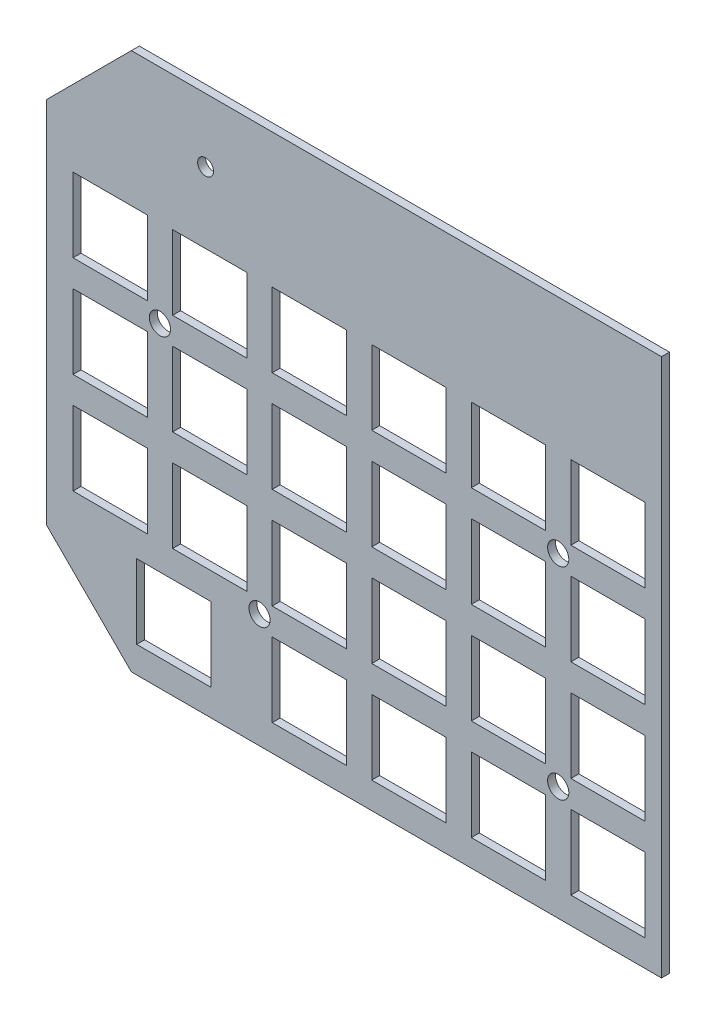
SolidWorks part; units mm, degrees
ref_plane "Plan de face" through (0, 0, 0) normal (0, 0, 1) x (1, 0, 0)
ref_plane "Plan de dessus" through (0, 0, 0) normal (0, 1, 0) x (1, 0, 0)
ref_plane "Plan de droite" through (0, 0, 0) normal (1, 0, 0) x (0, 0, -1)
sketch "Esquisse1" plane through (0, 0, 0) normal (0, 0, 1) x (1, 0, 0)
  line L0 (0, -85) -> (16, -101)
  line L4 (116, 0.5) -> (116, -101)
  line L5 (16, 0.5) -> (0, -15.5)
  line L7 (116, 0.5) -> (16, 0.5)
  line L8 (0, -15.5) -> (0, -85)
  line L9 (16, -101) -> (116, -101)
  dimension "D1" = 101.5
  dimension "D2" = 116
  dimension "D3" = 16
  dimension "D4" = 16
  dimension "D5" = 16
  dimension "D6" = 16
extrude "Boss.-Extru.1" add sketch "Esquisse1" along normal blind 1.5
sketch "Esquisse2" plane through (0, 0, 1.5) normal (0, 0, 1) x (1, 0, 0)
  line L0 (0, -15.5) -> (0, -85) construction
  line L1 (5, -24.85) -> (19, -24.85)
  line L2 (5, -24.85) -> (5, -38.85)
  line L3 (5, -38.85) -> (19, -38.85)
  line L4 (19, -24.85) -> (19, -38.85)
  line L5 (12, -38.85) -> (12, -24.85) construction
  line L6 (5, -31.85) -> (19, -31.85) construction
  line L7 (116, 0.5) -> (16, 0.5) construction
  line L12 (23.7813, -24.85) -> (23.7813, -38.85)
  line L13 (23.7813, -24.85) -> (37.7813, -24.85)
  line L14 (37.7813, -24.85) -> (37.7813, -38.85)
  line L15 (23.7813, -38.85) -> (37.7813, -38.85)
  line L16 (42.5626, -24.85) -> (42.5626, -38.85)
  line L17 (42.5626, -24.85) -> (56.5626, -24.85)
  line L18 (56.5626, -24.85) -> (56.5626, -38.85)
  line L19 (42.5626, -38.85) -> (56.5626, -38.85)
  line L20 (61.3438, -24.85) -> (61.3438, -38.85)
  line L21 (61.3438, -24.85) -> (75.3438, -24.85)
  line L22 (75.3438, -24.85) -> (75.3438, -38.85)
  line L23 (61.3438, -38.85) -> (75.3438, -38.85)
  line L24 (80.1251, -24.85) -> (80.1251, -38.85)
  line L25 (80.1251, -24.85) -> (94.1251, -24.85)
  line L26 (94.1251, -24.85) -> (94.1251, -38.85)
  line L27 (80.1251, -38.85) -> (94.1251, -38.85)
  line L28 (98.9064, -24.85) -> (98.9064, -38.85)
  line L29 (98.9064, -24.85) -> (112.9064, -24.85)
  line L30 (112.9064, -24.85) -> (112.9064, -38.85)
  line L31 (98.9064, -38.85) -> (112.9064, -38.85)
  line L32 (23.7813, -43.9) -> (23.7813, -57.9)
  line L33 (23.7813, -43.9) -> (37.7813, -43.9)
  line L34 (37.7813, -43.9) -> (37.7813, -57.9)
  line L35 (23.7813, -57.9) -> (37.7813, -57.9)
  line L36 (42.5626, -43.9) -> (42.5626, -57.9)
  line L37 (42.5626, -43.9) -> (56.5626, -43.9)
  line L38 (56.5626, -43.9) -> (56.5626, -57.9)
  line L39 (42.5626, -57.9) -> (56.5626, -57.9)
  line L40 (61.3438, -43.9) -> (61.3438, -57.9)
  line L41 (61.3438, -43.9) -> (75.3438, -43.9)
  line L42 (75.3438, -43.9) -> (75.3438, -57.9)
  line L43 (61.3438, -57.9) -> (75.3438, -57.9)
  line L44 (80.1251, -43.9) -> (80.1251, -57.9)
  line L45 (80.1251, -43.9) -> (94.1251, -43.9)
  line L46 (94.1251, -43.9) -> (94.1251, -57.9)
  line L47 (80.1251, -57.9) -> (94.1251, -57.9)
  line L48 (98.9064, -43.9) -> (98.9064, -57.9)
  line L49 (98.9064, -43.9) -> (112.9064, -43.9)
  line L50 (112.9064, -43.9) -> (112.9064, -57.9)
  line L51 (98.9064, -57.9) -> (112.9064, -57.9)
  line L52 (23.7813, -62.95) -> (23.7813, -76.95)
  line L53 (23.7813, -62.95) -> (37.7813, -62.95)
  line L54 (37.7813, -62.95) -> (37.7813, -76.95)
  line L55 (23.7813, -76.95) -> (37.7813, -76.95)
  line L56 (42.5626, -62.95) -> (42.5626, -76.95)
  line L57 (42.5626, -62.95) -> (56.5626, -62.95)
  line L58 (56.5626, -62.95) -> (56.5626, -76.95)
  line L59 (42.5626, -76.95) -> (56.5626, -76.95)
  line L60 (61.3438, -62.95) -> (61.3438, -76.95)
  line L61 (61.3438, -62.95) -> (75.3438, -62.95)
  line L62 (75.3438, -62.95) -> (75.3438, -76.95)
  line L63 (61.3438, -76.95) -> (75.3438, -76.95)
  line L64 (80.1251, -62.95) -> (80.1251, -76.95)
  line L65 (80.1251, -62.95) -> (94.1251, -62.95)
  line L66 (94.1251, -62.95) -> (94.1251, -76.95)
  line L67 (80.1251, -76.95) -> (94.1251, -76.95)
  line L68 (98.9064, -62.95) -> (98.9064, -76.95)
  line L69 (98.9064, -62.95) -> (112.9064, -62.95)
  line L70 (112.9064, -62.95) -> (112.9064, -76.95)
  line L71 (98.9064, -76.95) -> (112.9064, -76.95)
  line L72 (5, -43.9) -> (5, -57.9)
  line L73 (5, -43.9) -> (19, -43.9)
  line L74 (19, -43.9) -> (19, -57.9)
  line L75 (5, -57.9) -> (19, -57.9)
  line L76 (5, -62.95) -> (5, -76.95)
  line L77 (5, -62.95) -> (19, -62.95)
  line L78 (19, -62.95) -> (19, -76.95)
  line L79 (5, -76.95) -> (19, -76.95)
  line L112 (42.5626, -82) -> (42.5626, -96)
  line L113 (42.5626, -82) -> (56.5626, -82)
  line L114 (56.5626, -82) -> (56.5626, -96)
  line L115 (42.5626, -96) -> (56.5626, -96)
  line L116 (61.3438, -82) -> (61.3438, -96)
  line L117 (61.3438, -82) -> (75.3438, -82)
  line L118 (75.3438, -82) -> (75.3438, -96)
  line L119 (61.3438, -96) -> (75.3438, -96)
  line L120 (80.1251, -82) -> (80.1251, -96)
  line L121 (80.1251, -82) -> (94.1251, -82)
  line L122 (94.1251, -82) -> (94.1251, -96)
  line L123 (80.1251, -96) -> (94.1251, -96)
  line L124 (98.9064, -82) -> (98.9064, -96)
  line L125 (98.9064, -82) -> (112.9064, -82)
  line L126 (112.9064, -82) -> (112.9064, -96)
  line L127 (98.9064, -96) -> (112.9064, -96)
  line L128 (5, -82) -> (5, -96) [skipped]
  line L129 (5, -82) -> (19, -82) [skipped]
  line L130 (19, -82) -> (19, -96) [skipped]
  line L131 (5, -96) -> (19, -96) [skipped]
  line L132 (23.7813, -82) -> (23.7813, -96) [skipped]
  line L133 (23.7813, -82) -> (37.7813, -82) [skipped]
  line L134 (37.7813, -82) -> (37.7813, -96) [skipped]
  line L135 (23.7813, -96) -> (37.7813, -96) [skipped]
  line L137 (17, -82) -> (31, -82)
  line L138 (17, -82) -> (17, -96)
  line L139 (17, -96) -> (31, -96)
  line L140 (31, -82) -> (31, -96)
  line L141 (24, -96) -> (24, -82) construction
  line L142 (17, -89) -> (31, -89) construction
  line L143 (16, -101) -> (116, -101) construction
  line L144 (19, -38.85) -> (23.7813, -43.9) construction
  line L146 (94.1251, -38.85) -> (98.9064, -43.9) construction
  line L147 (94.1251, -76.95) -> (98.9064, -82) construction
  line L148 (37.7813, -76.95) -> (42.5626, -82) construction
  circle A4 centre (21.3906, -41.375) radius 2
  circle A5 centre (96.5158, -41.375) radius 2
  circle A6 centre (96.5158, -79.475) radius 2
  circle A7 centre (40.1719, -79.475) radius 2
  circle A8 centre (30, -11.5) radius 1.5
  point P0 (12, -31.85)
  point P19 (24, -89)
  dimension "D5" = 5
  dimension "D7" = 12
  dimension "D6" = 30
  dimension "D1" = 14
  dimension "D2" = 14
  dimension "D3" = 5
  dimension "D4" = 6
  dimension "D9" = 14
  dimension "D10" = 14
  dimension "D11" = 17
  dimension "D8" = 4
extrude "Enlèv. mat.-Extru.1" cut sketch "Esquisse2" against normal blind 1.5
